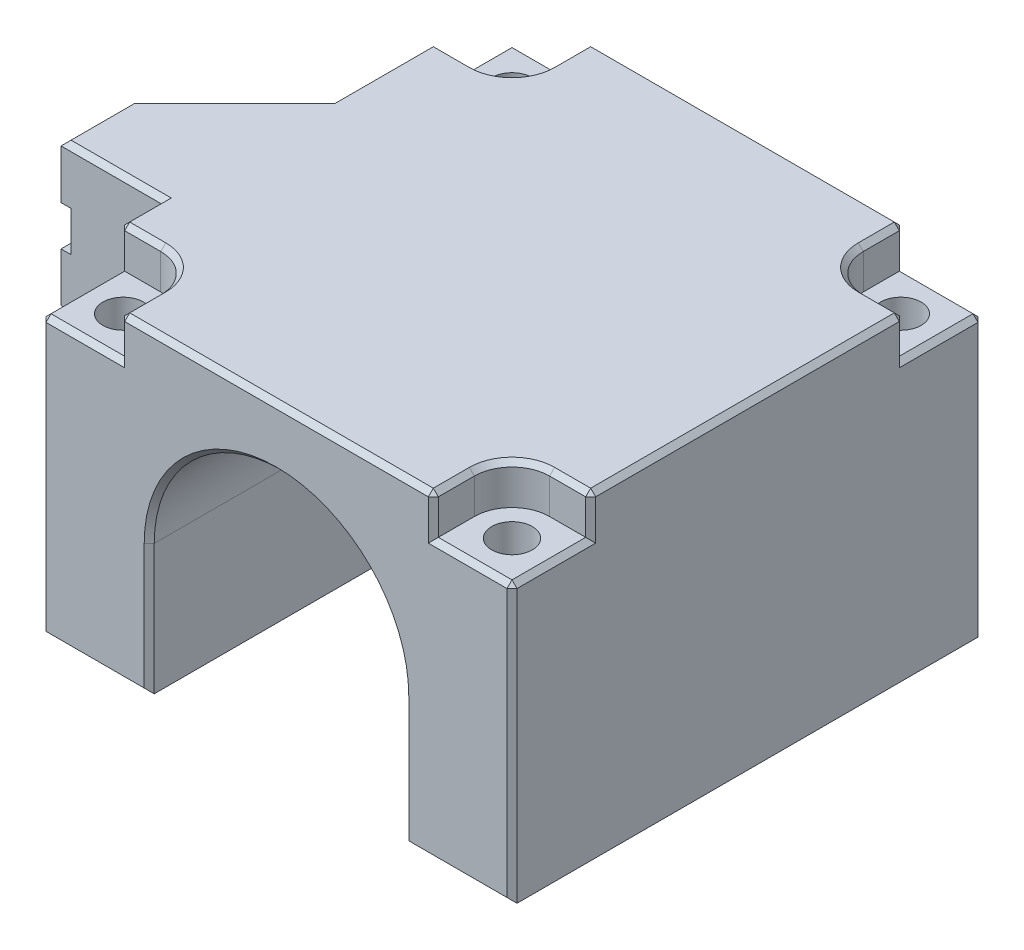
SolidWorks part; units mm, degrees
ref_plane "Front Plane" through (0, 0, 0) normal (0, 0, 1) x (1, 0, 0)
ref_plane "Top Plane" through (0, 0, 0) normal (0, 1, 0) x (1, 0, 0)
ref_plane "Right Plane" through (0, 0, 0) normal (1, 0, 0) x (0, 0, -1)
other "Graphic1"
other "Graphic (Closed) -1"
sketch "Sketch1" plane through (0, 0, 0) normal (0, 0, 1) x (1, 0, 0)
  line L0 (115, 94.15) -> (125.8, 94.15)
  line L1 (151.2, 94.15) -> (162, 94.15)
  line L2 (162, 94.15) -> (162, 102.35)
  line L3 (115, 102.35) -> (115, 94.15)
  line L4 (151.2, 94.15) -> (151.2, 107.15)
  line L5 (125.8, 107.15) -> (125.8, 94.15)
  arc A0 (162, 102.35) -> (115, 102.35) centre (138.5, 102.35) ccw
  arc A1 (151.2, 107.15) -> (125.8, 107.15) centre (138.5, 107.15) ccw
extrude "Boss-Extrude1" add sketch "Sketch1" along normal blind 47
sketch "Sketch2" plane through (0, 94.15, 0) normal (0, -1, 0) x (1, 0, 0)
  line L0 (115, 47) -> (125.8, 47) construction
  line L1 (115, 47) -> (115, 0) construction
  line L2 (162, 47) -> (162, 0) construction
  line L3 (119.1, 42.9) -> (157.9, 42.9) construction
  line L4 (119.1, 42.9) -> (119.1, 4.1) construction
  line L5 (119.1, 4.1) -> (157.9, 4.1) construction
  line L6 (157.9, 42.9) -> (157.9, 4.1) construction
  line L7 (151.2, 0) -> (162, 0) construction
  circle A0 centre (119.1, 42.9) radius 2.025
  circle A1 centre (157.9, 42.9) radius 2.025
  circle A2 centre (157.9, 4.1) radius 2.025
  circle A3 centre (119.1, 4.1) radius 2.025
  dimension "D2" = 4.1
  dimension "D3" = 4.05
  dimension "D1" = 4.1
  dimension "D4" = 4.1
  dimension "D5" = 4.1
extrude "Cut-Extrude1" cut sketch "Sketch2" against normal blind 47
ref_plane "Plane4" through (0, 121.45, 0) normal (0, -1, 0) x (-1, 0, 0)
sketch "Sketch3" plane through (0, 121.45, 0) normal (0, -1, 0) x (-1, 0, 0)
  line L0 (-124.8091, -8.1909) -> (-105, -28)
  line L1 (-105, -28) -> (-105, -35)
  line L2 (-105, -35) -> (-124.8091, -35)
  line L3 (-124.8091, -35) -> (-124.8091, -8.1909)
extrude "Boss-Extrude2" add sketch "Sketch3" along normal blind 10
sketch "Sketch4" plane through (0, 0, 35) normal (0, 0, 1) x (1, 0, 0)
  line L0 (105, 111.45) -> (105, 121.45) construction
  line L1 (105, 116.45) -> (106, 116.45)
  line L2 (105, 116.45) -> (105, 120.45)
  line L3 (105, 120.45) -> (106, 120.45)
  line L4 (106, 116.45) -> (106, 120.45)
  line L6 (112, 120.45) -> (115, 120.45)
  line L7 (112, 120.45) -> (112, 116.45)
  line L8 (112, 116.45) -> (115, 116.45)
  line L9 (115, 120.45) -> (115, 116.45)
extrude "Cut-Extrude2" cut sketch "Sketch4" against normal blind 19
sketch "Sketch5" plane through (105, 0, 0) normal (-1, 0, 0) x (0, 0, 1)
  line L1 (28, 116.45) -> (21, 116.45)
  line L2 (28, 116.45) -> (28, 120.45)
  line L3 (28, 120.45) -> (21, 120.45)
  line L4 (21, 116.45) -> (21, 120.45)
  point P6 (28, 116.45)
extrude "Cut-Extrude3" cut sketch "Sketch5" against normal blind 10
sketch "Sketch6" plane through (0, 0, 47) normal (0, 0, 1) x (1, 0, 0)
  line L0 (115, 102.35) -> (115, 125.85)
  line L1 (115, 125.85) -> (162, 125.85)
  line L2 (162, 125.85) -> (162, 102.35)
  line L3 (115, 102.35) -> (125.8, 102.35)
  line L4 (125.8, 94.15) -> (125.8, 107.15) construction
  line L5 (125.8, 102.35) -> (125.8, 107.15)
  line L6 (151.2, 107.15) -> (151.2, 102.35)
  line L7 (151.2, 107.15) -> (151.2, 94.15) construction
  line L8 (151.2, 102.35) -> (162, 102.35)
  arc A0 (125.8, 107.15) -> (151.2, 107.15) centre (138.5, 107.15) cw
  arc A1 (162, 102.35) -> (115, 102.35) centre (138.5, 102.35) ccw construction
extrude "Boss-Extrude3" add sketch "Sketch6" against normal up to vertex (47 mm away) up to point (162, 102.35, 0)
sketch "Sketch7" plane through (0, 102.35, 0) normal (0, -1, 0) x (1, 0, 0)
  circle A0 centre (119.1, 4.1) radius 2.025 construction
  circle A1 centre (157.9, 4.1) radius 2.025 construction
  circle A2 centre (157.9, 42.9) radius 2.025 construction
  circle A3 centre (119.1, 42.9) radius 2.025 construction
  circle A4 centre (119.1, 4.1) radius 2.025
  circle A5 centre (157.9, 4.1) radius 2.025
  circle A6 centre (157.9, 42.9) radius 2.025
  circle A7 centre (119.1, 42.9) radius 2.025
extrude "Cut-Extrude4" cut sketch "Sketch7" against normal blind 43
sketch "Sketch8" plane through (0, 125.85, 0) normal (0, 1, 0) x (1, 0, 0)
  line L0 (122.85, -4.1) -> (122.85, 0)
  line L1 (162, 0) -> (115, 0) construction
  line L2 (122.85, 0) -> (115, 0)
  line L3 (115, 0) -> (115, -7.85)
  line L4 (115, 0) -> (115, -47) construction
  line L5 (115, -7.85) -> (119.1, -7.85)
  line L6 (138.5, 0) -> (138.5, -47) construction
  line L7 (162, -47) -> (115, -47) construction
  line L8 (115, -23.5) -> (162, -23.5) construction
  line L9 (162, 0) -> (162, -47) construction
  line L10 (162, -7.85) -> (157.9, -7.85)
  line L11 (162, 0) -> (162, -7.85)
  line L12 (154.15, 0) -> (162, 0)
  line L13 (154.15, -4.1) -> (154.15, 0)
  line L14 (154.15, -42.9) -> (154.15, -47)
  line L15 (154.15, -47) -> (162, -47)
  line L16 (162, -47) -> (162, -39.15)
  line L17 (162, -39.15) -> (157.9, -39.15)
  line L18 (115, -39.15) -> (119.1, -39.15)
  line L19 (115, -47) -> (115, -39.15)
  line L20 (122.85, -47) -> (115, -47)
  line L21 (122.85, -42.9) -> (122.85, -47)
  arc A0 (119.1, -7.85) -> (122.85, -4.1) centre (119.1, -4.1) ccw
  arc A4 (157.9, -7.85) -> (154.15, -4.1) centre (157.9, -4.1) cw
  arc A5 (157.9, -39.15) -> (154.15, -42.9) centre (157.9, -42.9) ccw
  arc A6 (119.1, -39.15) -> (122.85, -42.9) centre (119.1, -42.9) cw
  dimension "D1" = 3.75
extrude "Cut-Extrude5" cut sketch "Sketch8" against normal blind 4
sketch "Sketch10" plane through (0, 121.45, 0) normal (0, 1, 0) x (1, 0, 0)
  line L4 (105, -35) -> (115, -35)
  line L5 (115, -35) -> (115, -18)
  line L6 (115, -18) -> (105, -28)
  line L7 (105, -28) -> (105, -35)
  line L8 (105, -35) -> (115, -35)
  line L9 (115, -35) -> (115, -18)
  line L10 (115, -18) -> (105, -28)
  line L11 (105, -28) -> (105, -35)
  dimension "D1" = 0
extrude "Boss-Extrude4" add sketch "Sketch10" along normal up to vertex (4.4 mm away) up to point (115, 125.85, 39.15)
sketch "Sketch11" plane through (0, 111.45, 0) normal (0, -1, 0) x (1, 0, 0)
  line L4 (115, 18) -> (115, 35)
  line L5 (115, 35) -> (105, 35)
  line L6 (105, 35) -> (105, 28)
  line L7 (105, 28) -> (115, 18)
  line L8 (115, 18) -> (115, 35)
  line L9 (115, 35) -> (105, 35)
  line L10 (105, 35) -> (105, 28)
  line L11 (105, 28) -> (115, 18)
  dimension "D1" = 0
extrude "Boss-Extrude5" add sketch "Sketch11" along normal blind 0.4
chamfer "Chamfer1" distance 0.5 angle 45 53 edges at (121.7517, 125.85, 40.2483) (117.05, 125.85, 39.15) (115, 125.85, 37.075) (110, 111.05, 35) (110, 125.85, 35) (105, 111.05, 31.5) (105, 125.85, 31.5) (110, 125.85, 23) (110, 111.05, 23) (115, 125.85, 12.925) (117.05, 125.85, 7.85) (121.7517, 125.85, 6.7517) (122.85, 125.85, 2.05) (138.5, 125.85, 0) (154.15, 125.85, 2.05) (155.2483, 125.85, 6.7517) (159.95, 125.85, 7.85) (162, 125.85, 23.5) (159.95, 125.85, 39.15) (155.2483, 125.85, 40.2483) (154.15, 125.85, 44.95) (138.5, 125.85, 47) (122.85, 125.85, 44.95) (154.15, 123.85, 47) (158.075, 121.85, 47) (162, 108, 47) (156.6, 94.15, 47) (151.2, 100.65, 47) (138.5, 119.85, 47) (125.8, 100.65, 47) (120.4, 94.15, 47) (115, 108, 47) (118.925, 121.85, 47) (122.85, 123.85, 47) (122.85, 123.85, 0) (118.925, 121.85, 0) (115, 108, 0) (120.4, 94.15, 0) (125.8, 100.65, 0) (138.5, 119.85, 0) (151.2, 100.65, 0) (156.6, 94.15, 0) (162, 108, 0) (158.075, 121.85, 0) (154.15, 123.85, 0) (115, 121.85, 43.075) (115, 123.85, 39.15) (162, 121.85, 43.075) (162, 123.85, 39.15) (162, 121.85, 3.925) (162, 123.85, 7.85) (115, 123.85, 7.85) (115, 121.85, 3.925)
